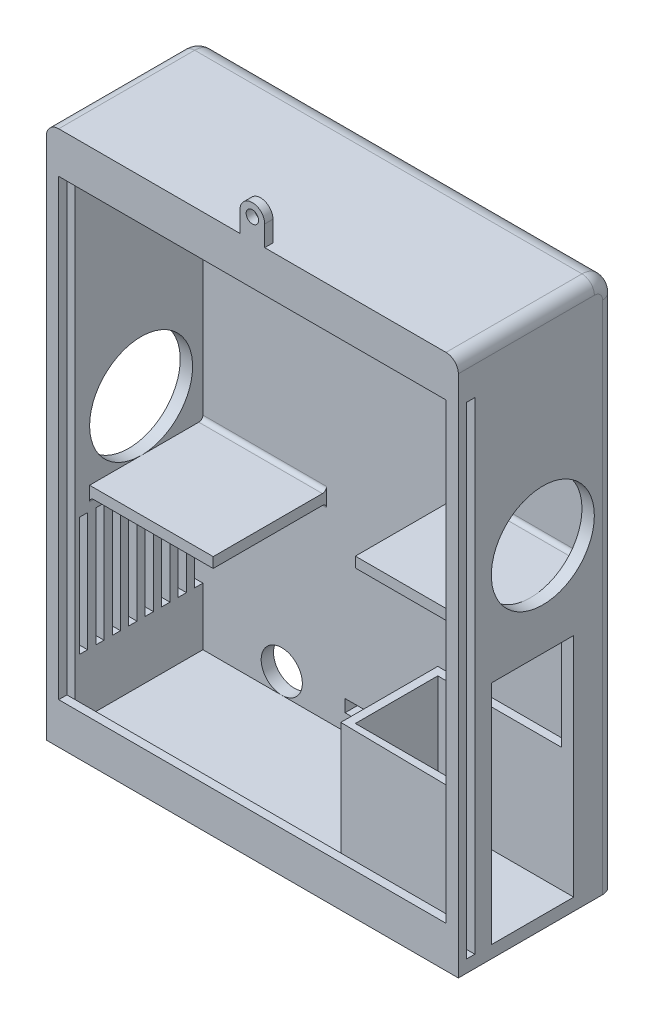
SolidWorks part; units mm, degrees
material "ABS"
ref_plane "Ön Düzlem" through (0, 0, 0) normal (0, 0, 1) x (1, 0, 0)
ref_plane "Üst Düzlem" through (0, 0, 0) normal (0, 1, 0) x (1, 0, 0)
ref_plane "Sağ Düzlem" through (0, 0, 0) normal (1, 0, 0) x (0, 0, -1)
sketch "Çizim1" plane through (0, 0, 0) normal (0, 0, 1) x (1, 0, 0)
  line L1 (-99.9072, 66.1787) -> (0.0928, 66.1787)
  line L2 (-99.9072, 66.1787) -> (-99.9072, -63.8213)
  line L3 (-99.9072, -63.8213) -> (0.0928, -63.8213)
  line L4 (0.0928, 66.1787) -> (0.0928, -63.8213)
  dimension "D1" = 130
  dimension "D2" = 100
extrude "Yükseklik-Ekstrüzyon1" add sketch "Çizim1" along normal blind 35
sketch "Çizim2" plane through (0, 0, 35) normal (0, 0, 1) x (1, 0, 0)
  line L0 (0.0928, 66.1787) -> (-99.9072, 66.1787) construction
  line L1 (-96.9072, 63.1787) -> (-2.9072, 63.1787)
  line L2 (-96.9072, 63.1787) -> (-96.9072, -60.8213)
  line L3 (-96.9072, -60.8213) -> (-2.9072, -60.8213)
  line L4 (-2.9072, 63.1787) -> (-2.9072, -60.8213)
  line L5 (-99.9072, 66.1787) -> (-99.9072, -63.8213) construction
  line L6 (0.0928, -63.8213) -> (0.0928, 66.1787) construction
  line L7 (-99.9072, -63.8213) -> (0.0928, -63.8213) construction
  dimension "D1" = 3
  dimension "D2" = 3
  dimension "D3" = 3
  dimension "D4" = 3
extrude "Kes-Ekstrüzyon1" cut sketch "Çizim2" against normal blind 27
sketch "Çizim3" plane through (0, 0, 0) normal (0, 0, -1) x (-1, 0, 0)
  line L0 (-0.0928, 66.1787) -> (99.9072, 66.1787) construction
  line L1 (13.9072, 56.1787) -> (85.9072, 56.1787)
  line L2 (13.9072, 56.1787) -> (13.9072, 31.1787)
  line L3 (13.9072, 31.1787) -> (85.9072, 31.1787)
  line L4 (85.9072, 56.1787) -> (85.9072, 31.1787)
  line L5 (99.9072, 66.1787) -> (99.9072, -63.8213) construction
  dimension "D1" = 72
  dimension "D2" = 25
  dimension "D3" = 10
  dimension "D4" = 14
extrude "Kes-Ekstrüzyon2" cut sketch "Çizim3" against normal blind 27
sketch "Çizim4" plane through (0, 0, 0) normal (0, 0, -1) x (-1, 0, 0)
  line L0 (99.9072, 66.1787) -> (99.9072, -63.8213) construction
  line L1 (14.9072, 21.1787) -> (84.9072, 21.1787)
  line L2 (14.9072, 21.1787) -> (14.9072, -53.8213)
  line L3 (14.9072, -53.8213) -> (84.9072, -53.8213)
  line L4 (84.9072, 21.1787) -> (84.9072, -53.8213)
  line L5 (13.9072, 31.1787) -> (85.9072, 31.1787) construction
  line L6 (-0.0928, -63.8213) -> (-0.0928, 66.1787) construction
  line L7 (37.4072, -53.8213) -> (62.4072, -53.8213)
  line L12 (37.4072, -53.8213) -> (37.4072, -56.8213)
  line L13 (37.4072, -56.8213) -> (62.4072, -56.8213)
  line L14 (62.4072, -53.8213) -> (62.4072, -56.8213)
  dimension "D1" = 70
  dimension "D2" = 75
  dimension "D3" = 15
  dimension "D4" = 10
  dimension "D5" = 25
  dimension "D6" = 3
  dimension "D7" = 37.5
extrude "Kes-Ekstrüzyon3" cut sketch "Çizim4" against normal blind 27 contours L13 L14 L7 L12
sketch "Çizim7" plane through (0.0928, 0, 0) normal (1, 0, 0) x (0, 0, -1)
  line L0 (-35, -63.8213) -> (0, -63.8213) construction
  line L1 (-30, -5.8213) -> (-10, -5.8213)
  line L2 (-30, -5.8213) -> (-30, -60.8213)
  line L3 (-30, -60.8213) -> (-10, -60.8213)
  line L4 (-10, -5.8213) -> (-10, -60.8213)
  line L5 (-35, -63.8213) -> (-35, 66.1787) construction
  dimension "D1" = 20
  dimension "D2" = 55
  dimension "D3" = 3
  dimension "D4" = 5
extrude "Kes-Ekstrüzyon5" cut sketch "Çizim7" against normal blind 27
sketch "Çizim8" plane through (-99.9072, 0, 0) normal (-1, 0, 0) x (0, 0, 1)
  line L0 (35, 66.1787) -> (35, -63.8213) construction
  line L1 (0, 66.1787) -> (0, -63.8213) construction
  circle A0 centre (18, 0) radius 12.5
  dimension "D1" = 17
  dimension "D2" = 17
  dimension "D3" = 18
extrude "Kes-Ekstrüzyon7" cut sketch "Çizim8" against normal blind 27
sketch "Çizim9" plane through (0.0928, 0, 0) normal (1, 0, 0) x (0, 0, -1)
  line L0 (-35, -63.8213) -> (-35, 66.1787) construction
  circle A0 centre (-21.5, 19.4187) radius 12.5
  dimension "D1" = 13.5
extrude "Kes-Ekstrüzyon8" cut sketch "Çizim9" against normal blind 27
sketch "Çizim12" plane through (0, 0, 8) normal (0, 0, 1) x (1, 0, 0)
  line L1 (-96.9072, 63.1787) -> (-2.9072, 63.1787)
  line L2 (-96.9072, 63.1787) -> (-96.9072, -60.8213)
  line L3 (-96.9072, -60.8213) -> (-2.9072, -60.8213)
  line L4 (-2.9072, 63.1787) -> (-2.9072, -60.8213)
extrude "Kes-Ekstrüzyon9" cut sketch "Çizim12" against normal blind 5
sketch "Çizim13" plane through (0.0928, 0, 0) normal (1, 0, 0) x (0, 0, -1)
  line L0 (-35, -63.8213) -> (-35, 66.1787) construction
  line L1 (-35, 1.1787) -> (-6.5468, 1.1787)
  line L2 (-35, 1.1787) -> (-35, 39.4148)
  line L3 (-35, 39.4148) -> (-6.5468, 39.4148)
  line L4 (-6.5468, 1.1787) -> (-6.5468, 39.4148)
extrude "Yükseklik-Ekstrüzyon2" add sketch "Çizim13" against normal blind 3
sketch "Çizim14" plane through (0.0928, 0, 0) normal (1, 0, 0) x (0, 0, -1)
  line L0 (0, -63.8213) -> (0, 66.1787) construction
  circle A0 centre (-17.5, 16.8523) radius 12.5
  dimension "D1" = 17.5
extrude "Kes-Ekstrüzyon10" cut sketch "Çizim14" against normal blind 12
sketch "Çizim15" plane through (0, 0, 0) normal (0, 0, -1) x (-1, 0, 0)
  line L0 (99.9072, -63.8213) -> (-0.0928, -63.8213) construction
  circle A2 centre (77.7702, -55.8213) radius 5
  dimension "D1" = 8
extrude "Kes-Ekstrüzyon12" cut sketch "Çizim15" against normal blind 12
sketch "Çizim16" plane through (-99.9072, 0, 0) normal (-1, 0, 0) x (0, 0, 1)
  line L0 (0, 66.1787) -> (0, -63.8213) construction
  line L1 (3, -18) -> (32, -18)
  line L2 (3, -18) -> (3, -46.8213)
  line L3 (3, -46.8213) -> (32, -46.8213)
  line L4 (32, -18) -> (32, -46.8213)
  line L5 (35, 63.1787) -> (35, -60.8213) construction
  line L6 (3, -60.8213) -> (35, -60.8213) construction
  circle A0 centre (18, 0) radius 12.5 construction
  dimension "D3" = 18
  dimension "D1" = 3
  dimension "D2" = 3
  dimension "D4" = 14
extrude "Kes-Ekstrüzyon13" cut sketch "Çizim16" against normal blind 12
sketch "Çizim17" plane through (-99.9072, 0, 0) normal (-1, 0, 0) x (0, 0, 1)
  line L0 (3, -46.8213) -> (32, -46.8213) construction
  line L1 (5, -46.8213) -> (7, -46.8213)
  line L2 (5, -46.8213) -> (5, -18)
  line L3 (5, -18) -> (7, -18)
  line L4 (7, -46.8213) -> (7, -18)
  line L5 (32, -18) -> (3, -18) construction
  line L6 (3, -18) -> (3, -46.8213) construction
  line L8 (9, -46.8213) -> (11, -46.8213)
  line L9 (9, -46.8213) -> (9, -18)
  line L10 (9, -18) -> (11, -18)
  line L11 (11, -46.8213) -> (11, -18)
  line L12 (13, -46.8213) -> (15, -46.8213)
  line L13 (13, -46.8213) -> (13, -18)
  line L14 (13, -18) -> (15, -18)
  line L15 (15, -46.8213) -> (15, -18)
  line L16 (17, -46.8213) -> (19, -46.8213)
  line L17 (17, -46.8213) -> (17, -18)
  line L18 (17, -18) -> (19, -18)
  line L19 (19, -46.8213) -> (19, -18)
  line L20 (21, -46.8213) -> (23, -46.8213)
  line L21 (21, -46.8213) -> (21, -18)
  line L22 (21, -18) -> (23, -18)
  line L23 (23, -46.8213) -> (23, -18)
  line L24 (25, -46.8213) -> (27, -46.8213)
  line L25 (25, -46.8213) -> (25, -18)
  line L26 (25, -18) -> (27, -18)
  line L27 (27, -46.8213) -> (27, -18)
  line L28 (29, -18) -> (31, -18)
  line L29 (29, -18) -> (29, -46.8213)
  line L30 (29, -46.8213) -> (31, -46.8213)
  line L31 (31, -18) -> (31, -46.8213)
  dimension "D1" = 2
  dimension "D2" = 2
  dimension "D3" = 2
  dimension "D4" = 2
  dimension "D5" = 2
  dimension "D6" = 2
  dimension "D7" = 2
  dimension "D8" = 2
  dimension "D9" = 2
  dimension "D10" = 2
  dimension "D11" = 2
  dimension "D12" = 2
  dimension "D13" = 2
  dimension "D14" = 2
extrude "Yükseklik-Ekstrüzyon3" add sketch "Çizim17" against normal blind 3
sketch "Çizim18" plane through (0, 0, 32) normal (0, 0, -1) x (-1, 0, 0)
  line L1 (96.9072, -18) -> (99.9072, -18)
  line L2 (96.9072, -18) -> (96.9072, -46.8213)
  line L3 (96.9072, -46.8213) -> (99.9072, -46.8213)
  line L4 (99.9072, -18) -> (99.9072, -46.8213)
extrude "Kes-Ekstrüzyon14" cut sketch "Çizim18" against normal blind 1
sketch "Çizim20" plane through (-99.9072, 0, 0) normal (-1, 0, 0) x (0, 0, 1)
  line L1 (35, 66.1787) -> (38, 66.1787)
  line L2 (35, 66.1787) -> (35, -63.8213)
  line L3 (35, -63.8213) -> (38, -63.8213)
  line L4 (38, 66.1787) -> (38, -63.8213)
  dimension "D1" = 3
extrude "Yükseklik-Ekstrüzyon4" add sketch "Çizim20" against normal blind 3
sketch "Çizim21" plane through (0.0928, 0, 0) normal (1, 0, 0) x (0, 0, -1)
  line L1 (-35, 66.1787) -> (-38, 66.1787)
  line L2 (-35, 66.1787) -> (-35, -63.8213)
  line L3 (-35, -63.8213) -> (-38, -63.8213)
  line L4 (-38, 66.1787) -> (-38, -63.8213)
  dimension "D1" = 3
extrude "Yükseklik-Ekstrüzyon5" add sketch "Çizim21" against normal blind 3
sketch "Çizim22" plane through (0, 66.1787, 0) normal (0, 1, 0) x (1, 0, 0)
  line L1 (-96.9072, -35) -> (-2.9072, -35)
  line L2 (-96.9072, -35) -> (-96.9072, -38)
  line L3 (-96.9072, -38) -> (-2.9072, -38)
  line L4 (-2.9072, -35) -> (-2.9072, -38)
extrude "Yükseklik-Ekstrüzyon6" add sketch "Çizim22" against normal blind 3
sketch "Çizim23" plane through (0, -60.8213, 0) normal (0, 1, 0) x (1, 0, 0)
  line L5 (-2.9072, -35) -> (-96.9072, -35)
  line L6 (-2.9072, -35) -> (-2.9072, -38)
  line L7 (-2.9072, -38) -> (-96.9072, -38)
  line L8 (-96.9072, -35) -> (-96.9072, -38)
  dimension "D1" = 3
extrude "Yükseklik-Ekstrüzyon8" add sketch "Çizim23" against normal blind 3
sketch "Çizim24" plane through (0, 63.1787, 0) normal (0, -1, 0) x (1, 0, 0)
  line L0 (-2.9072, 3) -> (-2.9072, 38) construction
  line L1 (-96.9072, 38) -> (-2.9072, 38)
  line L2 (-96.9072, 38) -> (-96.9072, 36)
  line L3 (-96.9072, 36) -> (-2.9072, 36)
  line L4 (-2.9072, 38) -> (-2.9072, 36)
  dimension "D1" = 2
extrude "Yükseklik-Ekstrüzyon9" add sketch "Çizim24" along normal blind 7
sketch "Çizim25" plane through (0, -60.8213, 0) normal (0, 1, 0) x (1, 0, 0)
  line L0 (-2.9072, -30) -> (-2.9072, -38) construction
  line L1 (-96.9072, -38) -> (-2.9072, -38)
  line L2 (-96.9072, -38) -> (-96.9072, -36)
  line L3 (-96.9072, -36) -> (-2.9072, -36)
  line L4 (-2.9072, -38) -> (-2.9072, -36)
  dimension "D1" = 2
extrude "Yükseklik-Ekstrüzyon10" add sketch "Çizim25" along normal blind 7
sketch "Çizim28" plane through (0.0928, 0, 0) normal (1, 0, 0) x (0, 0, -1)
  line L0 (-38, -63.8213) -> (0, -63.8213) construction
  line L1 (-38, -63.8213) -> (-36, -63.8213)
  line L2 (-38, -63.8213) -> (-38, -60.8213)
  line L3 (-38, -60.8213) -> (-36, -60.8213)
  line L4 (-36, -63.8213) -> (-36, -60.8213)
  line L5 (-36, -60.8213) -> (-34, -60.8213)
  line L6 (-36, -60.8213) -> (-36, -63.8213)
  line L7 (-36, -63.8213) -> (-34, -63.8213)
  line L8 (-34, -60.8213) -> (-34, -63.8213)
  line L10 (-36, -60.8213) -> (-34, -60.8213)
  line L11 (-36, -60.8213) -> (-36, 56.1787)
  line L12 (-36, 56.1787) -> (-34, 56.1787)
  line L13 (-34, -60.8213) -> (-34, 56.1787)
  dimension "D1" = 3
  dimension "D2" = 2
  dimension "D3" = 2
  dimension "D4" = 117
extrude "Kes-Ekstrüzyon16" cut sketch "Çizim28" against normal blind 119 contours L5 L13 L12 L11 region at (0.0928, -2.3213, 35)
sketch "Çizim30" plane through (0, 0, 38) normal (0, 0, 1) x (1, 0, 0)
  line L0 (-49.9072, 66.1787) -> (-49.9072, 76.155) construction
  line L10 (0.0928, 66.1787) -> (-99.9072, 66.1787) construction
  line L11 (-52.9072, 71.1668) -> (-52.9072, 66.1787)
  line L12 (-46.9072, 71.1668) -> (-46.9072, 66.1787)
  line L13 (-52.9072, 66.1787) -> (-46.9072, 66.1787)
  circle A1 centre (-49.9072, 71.1668) radius 3
  circle A2 centre (-49.9072, 71.1668) radius 1.5
  line M17 (0.0928, 66.1787) -> (-99.9072, 66.1787)
extrude "Yükseklik-Ekstrüzyon13" add sketch "Çizim30" against normal blind 2 contours L13 L0 A1 L11 | L0 L12 A1 M17 | L0 A1 A2 | A1 L0 A2 region at (-51.6102, 67.5798, 38) region at (-48.2042, 67.5798, 38) region at (-51.9811, 69.093, 38) region at (-49.8401, 68.9168, 38)
sketch "Çizim31" plane through (0, -60.8213, 0) normal (0, 1, 0) x (1, 0, 0)
  line L0 (-2.9072, -10) -> (-32.9072, -10) construction
  line L1 (-32.9072, -10) -> (-32.9072, -30)
  line L4 (-2.9072, -10) -> (-32.9072, -10)
  line L5 (-2.9072, -30) -> (-32.9072, -30)
  line L6 (-2.9072, -8) -> (-32.9072, -8)
  line L7 (-2.9072, -3) -> (-2.9072, -10) construction
  line L11 (-2.9072, -8) -> (-2.9072, -10)
  line L13 (-2.9072, -30) -> (-2.9072, -32)
  line L14 (-2.9072, -30) -> (-2.9072, -34) construction
  line L15 (-2.9072, -32) -> (-34.9072, -31.5432)
  line L18 (-32.9072, -10) -> (-32.9072, -8) construction
  line L19 (-32.9072, -8) -> (-34.9072, -8)
  line L20 (-34.9072, -8) -> (-34.9072, -31.5432)
  dimension "D1" = 30
  dimension "D2" = 2
  dimension "D3" = 2
extrude "Yükseklik-Ekstrüzyon14" add sketch "Çizim31" along normal blind 30
sketch "Çizim32" plane through (-2.9072, 0, 0) normal (-1, 0, 0) x (0, 0, 1)
  line L0 (5, 16.8523) -> (5, -3.5863) construction
  line L1 (30, 16.8523) -> (30, -3.5863) construction
  line L2 (17.5, 4.3523) -> (30, 4.3523) construction
  line L3 (30, 4.3523) -> (5, 4.3523)
  line L5 (30, 1.8523) -> (30, 4.3523)
  line L6 (5, 1.8523) -> (30, 1.8523)
  line L7 (5, 4.3523) -> (3, 4.3523)
  line L8 (3, -60.8213) -> (3, 63.1787) construction
  line L9 (3, 4.3523) -> (3, 1.8523)
  line L10 (3, 1.8523) -> (5, 1.8523)
  circle A0 centre (17.5, 16.8523) radius 12.5 construction
extrude "Yükseklik-Ekstrüzyon16" add sketch "Çizim32" along normal blind 30
sketch "Çizim33" plane through (-96.9072, 0, 0) normal (1, 0, 0) x (0, 0, -1)
  line L0 (-30.5, 0) -> (-30.5, -14.4441) construction
  line L1 (-18, -12.5) -> (-30.5, -12.5) construction
  line L2 (-30.5, -12.5) -> (-3, -12.5)
  line L3 (-3, 63.1787) -> (-3, -18) construction
  line L4 (-3, -12.5) -> (-3, -15)
  line L5 (-3, -15) -> (-30.5, -15)
  line L6 (-30.5, -15) -> (-30.5, -12.5)
  circle A0 centre (-18, 0) radius 12.5 construction
  dimension "D1" = 2.5
extrude "Yükseklik-Ekstrüzyon17" add sketch "Çizim33" along normal blind 30
fillet "Radyus2" radius 1 1 edges at (-81.9072, -12.5, 3)
fillet "Radyus3" radius 1 1 edges at (-17.9072, 4.3523, 3)
fillet "Radyus4" radius 5 1 edges at (-49.9072, 66.1787, 0)
fillet "Radyus5" radius 3 3 edges at (0.0928, 66.1787, 21.5) (0.0928, 64.7142, 1.4645) (0.0928, -1.3213, 0)
fillet "Radyus6" radius 3 3 edges at (-99.9072, 66.1787, 21.5) (-99.9072, 64.7142, 1.4645) (-99.9072, -1.3213, 0)
fillet "Radyus7" radius 1 1 edges at (-17.9072, 1.8523, 3)
fillet "Radyus8" radius 1 1 edges at (-81.9072, -15, 3)
fillet "Radyus9" radius 1 3 edges at (-96.9072, -17, 3) (-96.9072, -15.2929, 3.2929) (-96.9072, -15, 17.25)
fillet "Radyus12" radius 1 1 edges at (-2.9072, 1.8523, 17) tangent propagation no
